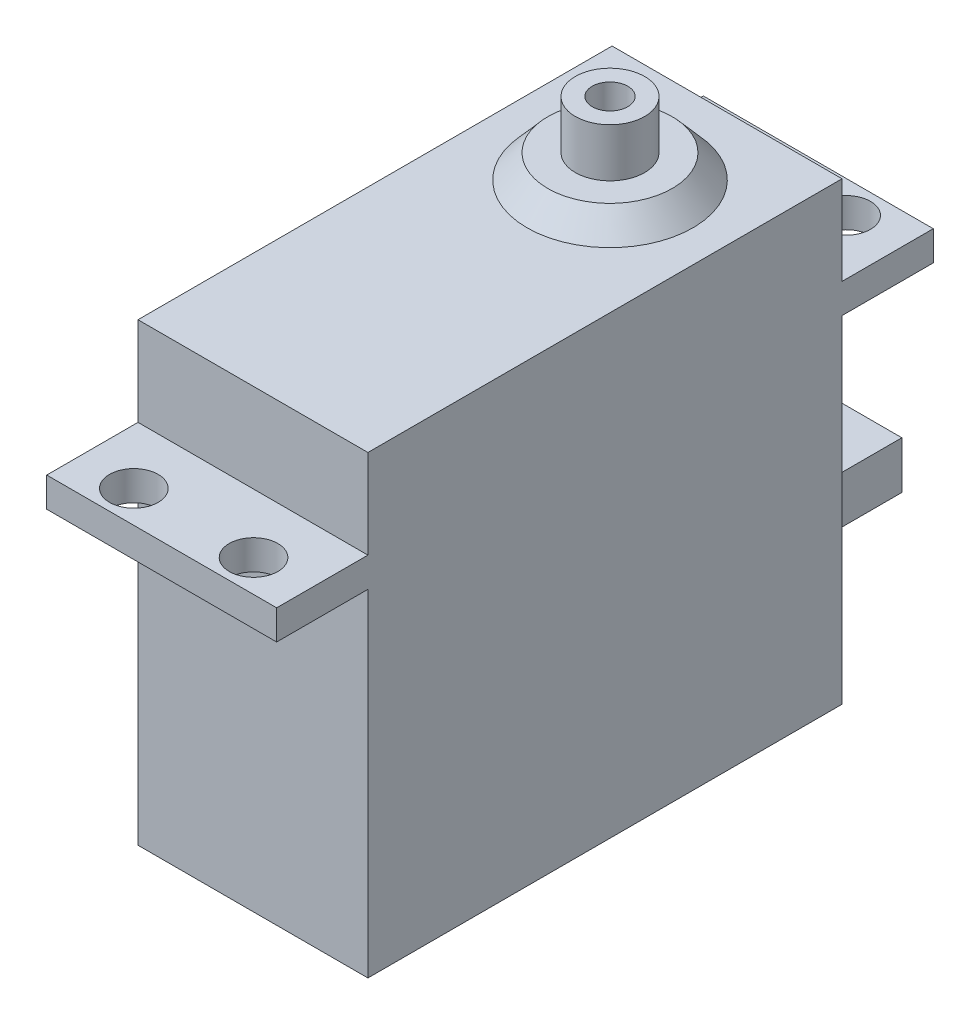
SolidWorks part; units mm, degrees
ref_plane "정면" through (0, 0, 0) normal (0, 0, 1) x (1, 0, 0)
ref_plane "윗면" through (0, 0, 0) normal (0, 1, 0) x (1, 0, 0)
ref_plane "우측면" through (0, 0, 0) normal (1, 0, 0) x (0, 0, -1)
sketch "스케치1" plane through (0, 0, 0) normal (0, 1, 0) x (1, 0, 0)
  line L0 (-9.7, 20) -> (9.7, 20)
  line L1 (-9.7, 20) -> (9.7, 20)
  line L2 (-9.7, 20) -> (-9.7, -20)
  line L3 (-9.7, -20) -> (9.7, -20)
  line L4 (9.7, 20) -> (9.7, -20)
  line L5 (-9.7, 20) -> (9.7, -20) construction
  line L6 (-9.7, -20) -> (9.7, 20) construction
  line L7 (-9.7, 20) -> (-9.7, 27.7)
  line L8 (9.7, 20) -> (9.7, 27.7)
  line L9 (-9.7, 27.7) -> (9.7, 27.7)
  line L10 (-9.7, -20) -> (9.7, -20)
  line L11 (-9.7, -20) -> (-9.7, -27.7)
  line L12 (9.7, -20) -> (9.7, -27.7)
  line L13 (-9.7, -27.7) -> (9.7, -27.7)
  line L14 (0, 0) -> (24.2731, 0) construction
  circle A0 centre (5.05, 25) radius 2.05
  circle A1 centre (-5.05, 25) radius 2.05
  circle A2 centre (5.05, -25) radius 2.05
  circle A3 centre (-5.05, -25) radius 2.05
  point P0 (0, 0)
  dimension "D4" = 4.1
  dimension "D1" = 19.4
  dimension "D2" = 40
  dimension "D3" = 55.4
  dimension "D5" = 4.65
  dimension "D6" = 4.65
  dimension "D7" = 2.7
extrude "보스-돌출1" add sketch "스케치1" along normal blind 2.5 contours L4 L0 L2 L3 | L11 L13 L12 L3 | L9 L7 L0 L8 region at (0, 0, -23.6031) region at (0, 0, 0) region at (0, 0, 23.6031)
extrude "보스-돌출2" add sketch "스케치1<3>" against normal blind 28.4 contours L4 L0 L2 L3 region at (0, 0, 0)
sketch "스케치1<3>" plane through (0, 0, 0) normal (0, 1, 0) x (1, 0, 0) same geometry as "스케치1"
extrude "보스-돌출3" add sketch "스케치1<4>" along normal blind 7.5 from surface contours L4 L0 L2 L3 region at (0, 0, 0) starting at face at (0, 2.5, 0)
sketch "스케치1<4>" plane through (0, 0, 0) normal (0, 1, 0) x (1, 0, 0) same geometry as "스케치1"
sketch "스케치2" plane through (0, 10, 0) normal (0, 1, 0) x (1, 0, 0)
  line L1 (9.7, -20) -> (-9.7, -20) construction
  circle A0 centre (0, 10.125) radius 2.925
  dimension "D1" = 5.85
  dimension "D2" = 30.125
extrude "보스-돌출4" add sketch "스케치2" along normal blind 6.1
sketch "스케치3" plane through (0, -28.4, 0) normal (0, -1, 0) x (1, 0, 0)
  line L1 (-9.7, 20) -> (9.7, 20) construction
  circle A0 centre (0, -10.125) radius 7
  dimension "D1" = 14
  dimension "D2" = 30.125
ref_plane "평면1" through (0, -31.4, 0) normal (0, -1, 0) x (-1, 0, 0)
sketch "스케치4" plane through (0, -31.4, 0) normal (0, -1, 0) x (-1, 0, 0)
  circle A0 centre (0, 10.125) radius 4
  dimension "D1" = 8
loft "로프트1" add profiles "스케치3", "스케치4" connector at (1.4626, -28.4, -3.2795) connector at (2.267, -31.4, -6.8294)
extrude "보스-돌출5" add sketch "스케치4<2>" along normal blind 1 contours A0
sketch "스케치4<2>" plane through (0, -31.4, 0) normal (0, -1, 0) x (-1, 0, 0) same geometry as "스케치4"
sketch "스케치6" plane through (0, 10, 0) normal (0, 1, 0) x (1, 0, 0)
  circle A0 centre (0, 10.125) radius 7
  dimension "D1" = 14
ref_plane "평면3" through (0, 12, 0) normal (0, 1, 0) x (1, 0, 0)
sketch "스케치7" plane through (0, 12, 0) normal (0, 1, 0) x (1, 0, 0)
  circle A0 centre (0, 10.125) radius 5.25
  dimension "D1" = 10.5
loft "로프트2" add profiles "스케치6", "스케치7" connector at (-3.221, 10, -3.9101) connector at (-2.4479, 12, -5.4806)
sketch "스케치8" plane through (0, 16.1, 0) normal (0, 1, 0) x (1, 0, 0)
  circle A0 centre (0, 10.125) radius 1.5
  dimension "D1" = 3
extrude "컷-돌출1" cut sketch "스케치8" against normal up to surface (6.1 mm away) up to face at (0, 10, -3.125)
sketch "스케치9" plane through (0, -32.4, 0) normal (0, -1, 0) x (1, 0, 0)
  circle A0 centre (0, -10.125) radius 1.5
  dimension "D1" = 3
extrude "컷-돌출2" cut sketch "스케치9" against normal up to surface (4 mm away) up to face at (0, -28.4, -17.125)
sketch "스케치10" plane through (0, 0, -20) normal (0, 0, -1) x (-1, 0, 0)
  line L0 (9.7, -28.4) -> (-9.7, -28.4) construction
  line L1 (-4, -17.4) -> (4, -17.4)
  line L2 (-4, -17.4) -> (-4, -23.4)
  line L3 (-4, -23.4) -> (4, -23.4)
  line L4 (4, -17.4) -> (4, -23.4)
  line L5 (-4, -17.4) -> (4, -23.4) construction
  line L6 (-4, -23.4) -> (4, -17.4) construction
  point P0 (0, -20.4)
  dimension "D1" = 8
  dimension "D2" = 6
  dimension "D3" = 5
extrude "보스-돌출6" add sketch "스케치10" along normal blind 2
sketch "스케치11" plane through (0, 0, -22) normal (0, 0, -1) x (-1, 0, 0)
  line L0 (0, -23.4) -> (0, -17.4) construction
  line L1 (-4, -23.4) -> (4, -23.4) construction
  line L2 (4, -17.4) -> (-4, -17.4) construction
  line L3 (-4, -20.4) -> (0, -20.4) construction
  line L4 (-4, -17.4) -> (-4, -23.4) construction
  line L6 (-2.75, -22.4) -> (2.75, -22.4)
  line L7 (-2.75, -22.4) -> (-2.75, -18.4)
  line L8 (-2.75, -18.4) -> (2.75, -18.4)
  line L9 (2.75, -22.4) -> (2.75, -18.4)
  line L10 (-2.75, -22.4) -> (2.75, -18.4) construction
  line L11 (-2.75, -18.4) -> (2.75, -22.4) construction
  dimension "D1" = 4
  dimension "D2" = 5.5
extrude "보스-돌출7" add sketch "스케치11" along normal blind 10
